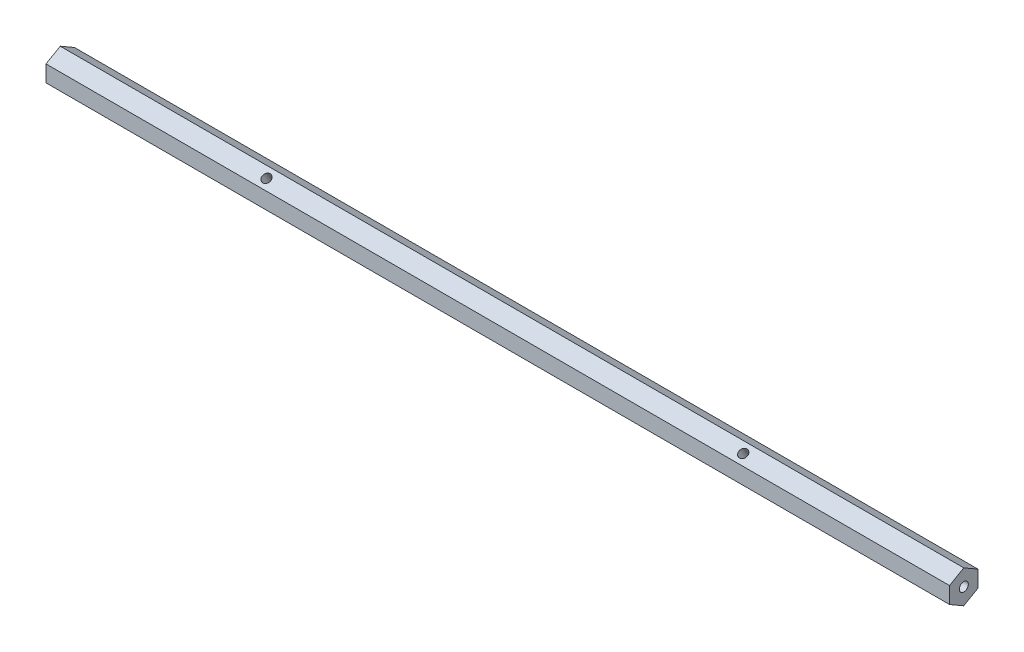
SolidWorks part; units mm, degrees
material "6061-T6 (SS)"
ref_plane "Front" through (0, 0, 0) normal (0, 0, 1) x (1, 0, 0)
ref_plane "Top" through (0, 0, 0) normal (0, 1, 0) x (1, 0, 0)
ref_plane "Right" through (0, 0, 0) normal (1, 0, 0) x (0, 0, -1)
ref_axis "Axis1" through (-80.9, 0, 0) along (1, 0, 0)
sketch "Sketch1" plane through (0, 0, 0) normal (1, 0, 0) x (0, 0, -1)
  line L1 (0, 7.3323) -> (-6.35, 3.6662)
  line L2 (-6.35, 3.6662) -> (-6.35, -3.6662)
  line L3 (-6.35, -3.6662) -> (0, -7.3323)
  line L4 (0, -7.3323) -> (6.35, -3.6662)
  line L5 (6.35, -3.6662) -> (6.35, 3.6662)
  line L6 (6.35, 3.6662) -> (0, 7.3323)
  circle A0 centre (0, 0) radius 6.35 construction
  dimension "D1" = 12.7
extrude "Boss-Extrude1" add sketch "Sketch1" along normal up to surface (403.225 mm away)
hole_wizard "#10-32 Tapped Hole1" positions "Sketch2" profile "Sketch3" tap size "#10-32" standard "ANSI Inch"
sketch "Sketch2" plane through (403.225, 0, 0) normal (1, 0, 0) x (0, 0, -1)
  point P0 (0, 0)
sketch "Sketch3" plane through (403.225, 0, 0) normal (0, 1, 0) x (0, 0, -1)
  line L0 (0, 0) -> (0, 13.2529)
  line L1 (0, 13.2529) -> (2.0193, 12.0396)
  line L2 (2.0193, 12.0396) -> (2.0193, 0)
  line L5 (2.0193, 0) -> (0, 0)
  line L10 (0, 13.2529) -> (-2.0193, 12.0396) construction
  line L11 (0, -6.35) -> (0, 107.95) construction
  dimension "Tap Drill Dia." = 4.0386
  dimension "Tap Drill Depth" = 12.0396
  dimension "Drill Angle" = 118
cosmetic thread "Hole Thread1" parameters "D1"=9.652, "D2"=4.826
hole_wizard "#10-32 Tapped Hole2" positions "Sketch4" profile "Sketch5" tap size "#10-32" standard "ANSI Inch"
sketch "Sketch4" plane through (0, 0, 0) normal (-1, 0, 0) x (0, 0, 1)
  point P0 (0, 0)
sketch "Sketch5" plane through (0, 0, 0) normal (0, 1, 0) x (0, 0, 1)
  line L0 (0, 0) -> (0, 13.2529)
  line L1 (0, 13.2529) -> (2.0193, 12.0396)
  line L2 (2.0193, 12.0396) -> (2.0193, 0)
  line L5 (2.0193, 0) -> (0, 0)
  line L10 (0, 13.2529) -> (-2.0193, 12.0396) construction
  line L11 (0, -6.35) -> (0, 107.95) construction
  dimension "Tap Drill Dia." = 4.0386
  dimension "Tap Drill Depth" = 12.0396
  dimension "Drill Angle" = 118
cosmetic thread "Hole Thread2" parameters "D1"=9.652, "D2"=4.826
sketch "Sketch6" plane through (0, 5.4993, 3.175) normal (0, 0.866, 0.5) x (1, 0, 0)
  line L0 (0, 7.3323) -> (0, 3.6662) construction
  line L3 (0, 0) -> (95.25, 0) construction
  line L4 (0, 3.6662) -> (0, -3.6662) construction
  line L9 (307.975, 0) -> (403.225, 0) construction
  line L10 (403.225, -3.6662) -> (403.225, 3.6662) construction
  circle A0 centre (95.25, 0) radius 1.905
  circle A1 centre (307.975, 0) radius 1.905
  dimension "D1" = 3.81
  dimension "D2" = 95.25
extrude "Cut-Extrude1" cut sketch "Sketch6" against normal through all
